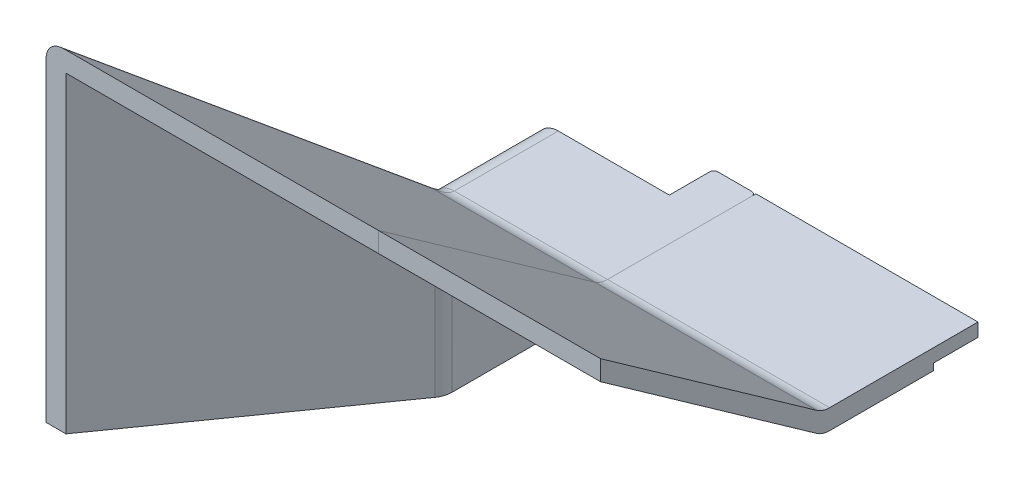
SolidWorks part; units mm, degrees
ref_plane "前视基准面" through (0, 0, 0) normal (0, 0, 1) x (1, 0, 0)
ref_plane "上视基准面" through (0, 0, 0) normal (0, 1, 0) x (1, 0, 0)
ref_plane "右视基准面" through (0, 0, 0) normal (1, 0, 0) x (0, 0, -1)
other "Configuration Table"
sketch "草图1" plane through (0, 0, 0) normal (0, 0, 1) x (1, 0, 0)
  line L0 (0, 0) -> (0, 79)
  line L1 (0, 79) -> (79, 79)
  line L2 (79, 79) -> (79, 70)
  line L3 (79, 70) -> (9, 70)
  line L4 (9, 70) -> (9, 0)
  line L5 (9, 0) -> (0, 0)
  dimension "D1" = 9
  dimension "D2" = 9
  dimension "D3" = 70
  dimension "D4" = 70
ref_plane "基准面1" through (0, 0, 100) normal (0, 0, 1) x (1, 0, 0)
sketch "草图2" plane through (0, 0, 100) normal (0, 0, 1) x (1, 0, 0)
  line L0 (0, 79) -> (-70.7107, 149.7107) construction
  line L1 (0, 0) -> (0, 79) construction
  line L2 (-70.7107, 149.7107) -> (-70.7107, 0)
  line L3 (-70.7107, 0) -> (-61.7107, 0)
  line L4 (-61.7107, 0) -> (-61.7107, 140.7107)
  line L5 (-61.7107, 140.7107) -> (79, 140.7107)
  line L6 (79, 140.7107) -> (79, 149.7107)
  line L7 (79, 149.7107) -> (-70.7107, 149.7107)
  line L8 (0, 0) -> (0, 79) construction
  line L9 (0, 79) -> (79, 79) construction
  point P13 (0, 0)
  dimension "D1" = 135
  dimension "D2" = 9
  dimension "D3" = 100
  dimension "D4" = 79
loft "放样1" add profiles "草图1", "草图2" connector at (79, 79, 0) connector at (79, 149.2162, 100)
sketch "草图4" plane through (0, 0, 0) normal (0, 0, -1) x (-1, 0, 0)
  line L7 (-9, 0) -> (0, 0)
  line L8 (0, 0) -> (0, 79)
  line L9 (0, 79) -> (-79, 79)
  line L10 (-79, 79) -> (-79, 70)
  line L11 (-79, 70) -> (-77.7656, 70)
  line L12 (-77.7656, 70) -> (-9, 70)
  line L13 (-9, 70) -> (-9, 0)
  line L14 (-9, 0) -> (0, 0)
  line L15 (0, 0) -> (0, 79)
  line L16 (0, 79) -> (-79, 79)
  line L17 (-79, 79) -> (-79, 70)
  line L18 (-79, 70) -> (-77.7656, 70)
  line L19 (-77.7656, 70) -> (-9, 70)
  line L20 (-9, 70) -> (-9, 0)
  dimension "D1" = 0
extrude "凸台-拉伸1" add sketch "草图4" along normal blind 50
sketch "草图9" plane through (0, 0, -50) normal (0, 0, -1) x (-1, 0, 0)
  line L0 (-9, 70) -> (-9, 0) construction
  line L1 (-9, 70) -> (-55, 70)
  line L2 (-9, 70) -> (-9, 30)
  line L3 (-15, 64) -> (-55, 64)
  line L4 (-55, 70) -> (-55, 64)
  line L6 (-15, 64) -> (-15, 30)
  line L7 (-15, 30) -> (-9, 30)
  point P8 (-15, 64)
  point P11 (-15, 30.9183)
  point P12 (-15, 29.2856)
  point P13 (-15, 29.7456)
  dimension "D1" = 6
  dimension "D2" = 46
  dimension "D3" = 6
  dimension "D4" = 40
extrude "凸台-拉伸3" add sketch "草图9" against normal blind 6
fillet "圆角1" radius 10 8 edges
sketch "草图11" plane through (0, 0, -44) normal (0, 0, 1) x (1, 0, 0)
  circle A0 centre (12, 45) radius 1.55
  circle A1 centre (12, 65) radius 1.55
  circle A2 centre (30, 67) radius 1.55
  circle A3 centre (50, 67) radius 1.55
  dimension "D1" = 3.1
extrude "切除-拉伸1" cut sketch "草图11" against normal through all
sketch "草图12" plane through (0, 0, -50) normal (0, 0, -1) x (-1, 0, 0)
  line L0 (0, 19) -> (0, 0)
  line L1 (0, 0) -> (0, 69) construction
  line L2 (0, 0) -> (-6, 0)
  line L3 (-9, 0) -> (0, 0) construction
  line L5 (-6, 0) -> (-6, 19)
  line L6 (0, 19) -> (-6, 19)
  line L7 (-2.9289, 76.0711) -> (-93.7798, -14.7798) construction
  line L8 (0, 0) -> (0, 69) construction
  line L9 (-60, 79) -> (-60, 73)
  line L10 (-79, 73) -> (-60, 73)
  line L11 (-79, 79) -> (-79, 73)
  line L12 (-60, 79) -> (-79, 79)
  arc A0 (0, 69) -> (-10, 79) centre (-10, 69) ccw construction
  dimension "D1" = 19
  dimension "D2" = 6
  dimension "D3" = 45
extrude "凸台-拉伸4" add sketch "草图12" along normal blind 20
fillet "圆角2" radius 2 9 edges at (3, 0, -70) (3, 19, -70) (9, 30, -47) (15, 30, -47) (15, 64, -47) (55, 70, -47) (55, 64, -47) (79, 76, -70) (60, 76, -70)
sketch "草图13" plane through (79, 0, 0) normal (1, 0, 0) x (0, 0, -1)
  line L0 (70, 79) -> (68, 79) construction
  line L1 (70, 79) -> (70, 73) construction
  line L9 (50, 73) -> (68, 73)
  line L10 (68, 73) -> (68, 79)
  line L11 (68, 79) -> (3.1784, 79)
  line L12 (-2.5951, 80.835) -> (-100, 149.7107)
  line L13 (-100, 149.7107) -> (-100, 149.2162)
  line L14 (-100, 149.2162) -> (-100, 140.7107)
  line L15 (-100, 140.7107) -> (-2.5951, 71.835)
  line L16 (3.1784, 70) -> (50, 70)
  line L17 (50, 70) -> (50, 73)
  line L18 (50, 73) -> (70, 73)
  line L19 (70, 73) -> (70, 79)
  line L20 (70, 79) -> (3.1784, 79)
  line L21 (-2.5951, 80.835) -> (-100, 149.7107)
  line L22 (-100, 149.7107) -> (-100, 149.2162)
  line L23 (-100, 149.2162) -> (-100, 140.7107)
  line L24 (-100, 140.7107) -> (-2.5951, 71.835)
  line L25 (3.1784, 70) -> (50, 70)
  line L26 (50, 70) -> (50, 73)
  arc A2 (-2.5951, 80.835) -> (3.1784, 79) centre (3.1784, 89) ccw
  arc A3 (-2.5951, 71.835) -> (3.1784, 70) centre (3.1784, 80) ccw
  arc A4 (-2.5951, 80.835) -> (3.1784, 79) centre (3.1784, 89) ccw
  arc A5 (-2.5951, 71.835) -> (3.1784, 70) centre (3.1784, 80) ccw
  point P6 (70, 73)
  point P9 (70, 79)
  point P17 (69.6615, 79)
  dimension "D1" = 0
extrude "凸台-拉伸5" add sketch "草图13" along normal blind 100 separate body
